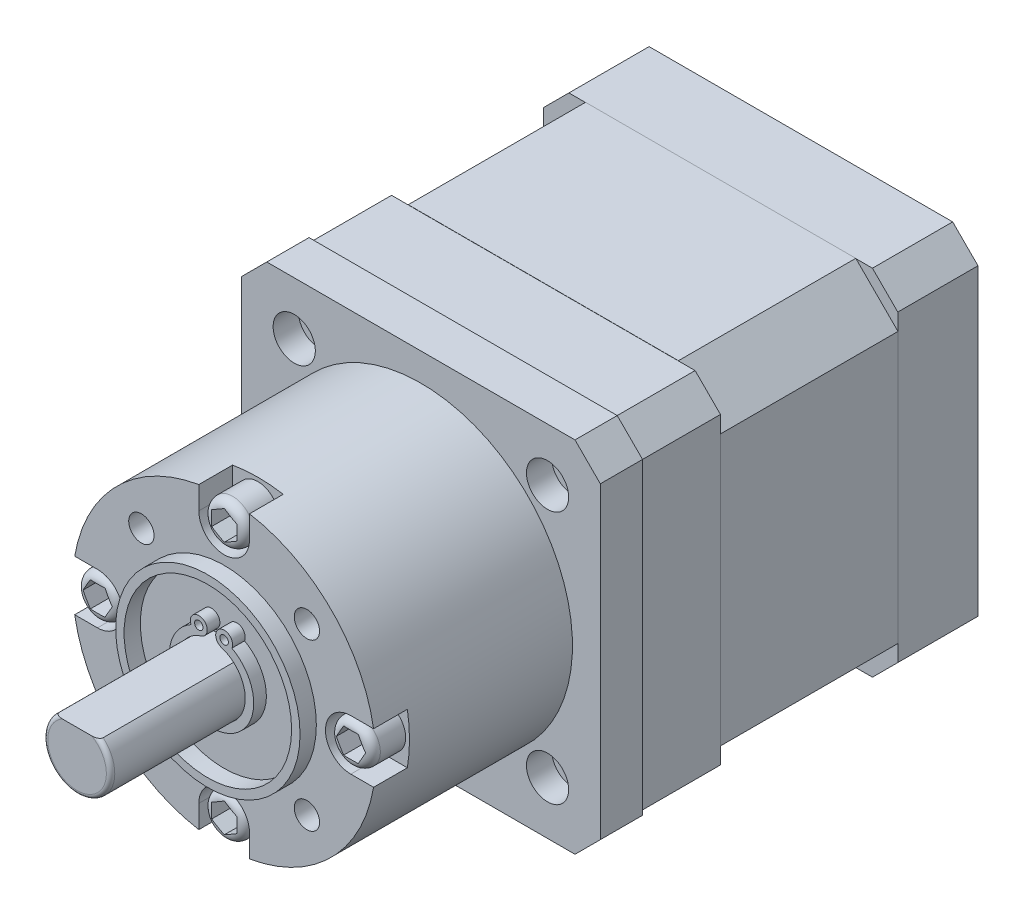
SolidWorks part; units mm, degrees
ref_plane "Front Plane" through (0, 0, 0) normal (0, 0, 1) x (1, 0, 0)
ref_plane "Top Plane" through (0, 0, 0) normal (0, 1, 0) x (1, 0, 0)
ref_plane "Right Plane" through (0, 0, 0) normal (1, 0, 0) x (0, 0, -1)
sketch "Sketch1" plane through (0, 0, 0) normal (0, 0, 1) x (1, 0, 0)
  line L1 (-21, 21) -> (21, 21)
  line L2 (-21, 21) -> (-21, -21)
  line L3 (-21, -21) -> (21, -21)
  line L4 (21, 21) -> (21, -21)
  line L5 (-21, 21) -> (21, -21) construction
  line L6 (-21, -21) -> (21, 21) construction
  point P0 (0, 0)
  dimension "D1" = 42
  dimension "D2" = 42
extrude "Boss-Extrude1" add sketch "Sketch1" along normal blind 21
chamfer "Chamfer1" distance 5 angle 45 4 edges at (-21, -21, 10.5) (-21, 21, 10.5) (21, -21, 10.5) (21, 21, 10.5)
ref_plane "Plane1" through (0, 0, 10.5) normal (0, 0, 1) x (1, 0, 0)
sketch "Sketch2" plane through (0, 0, 21) normal (0, 0, 1) x (1, 0, 0)
  line L1 (-20.975, 20.975) -> (20.975, 20.975)
  line L2 (-20.975, 20.975) -> (-20.975, -20.975)
  line L3 (-20.975, -20.975) -> (20.975, -20.975)
  line L4 (20.975, 20.975) -> (20.975, -20.975)
  line L5 (-20.975, 20.975) -> (20.975, -20.975) construction
  line L6 (-20.975, -20.975) -> (20.975, 20.975) construction
  point P0 (0, 0)
  dimension "D1" = 41.95
extrude "Boss-Extrude2" add sketch "Sketch2" along normal blind 9.5
mirror "Mirror1" about plane through (0, 0, 10.5) normal (0, 0, 1) of "Boss-Extrude2"
sketch "Sketch3" plane through (0, 0, 30.5) normal (0, 0, 1) x (1, 0, 0)
  circle A0 centre (0, 0) radius 17.95
  dimension "D1" = 35.9
extrude "Boss-Extrude3" add sketch "Sketch3" along normal blind 24.3
sketch "Sketch4" plane through (0, 0, -9.5) normal (0, 0, -1) x (-1, 0, 0)
  line L1 (-16, 16) -> (16, 16) construction
  line L2 (-16, 16) -> (-16, -16) construction
  line L3 (-16, -16) -> (16, -16) construction
  line L4 (16, 16) -> (16, -16) construction
  line L5 (-16, 16) -> (16, -16) construction
  line L6 (-16, -16) -> (16, 16) construction
  circle A0 centre (16, 16) radius 2
  circle A1 centre (16, -16) radius 2
  circle A2 centre (-16, -16) radius 2
  circle A3 centre (-16, 16) radius 2
  point P0 (0, 0)
  point P10 (0, 0)
  point P13 (0, 0)
  point P16 (0, 0)
  point P19 (0, 0)
  dimension "D2" = 4
  dimension "D4" = 16
  dimension "D1" = 32
  dimension "D3" = 4
extrude "Cut-Extrude1" cut sketch "Sketch4" against normal blind 1
sketch "Sketch5" plane through (0, 0, -8.5) normal (0, 0, -1) x (-1, 0, 0)
  line L0 (15.75, -14.5) -> (16.25, -14.5)
  line L1 (16.25, 14.5) -> (15.75, 14.5)
  line L2 (16.25, 14.5) -> (16.25, 17.5)
  line L3 (16.25, 17.5) -> (15.75, 17.5)
  line L4 (15.75, 14.5) -> (15.75, 17.5)
  line L5 (16.25, 14.5) -> (15.75, 17.5) construction
  line L6 (16.25, 17.5) -> (15.75, 14.5) construction
  line L7 (14.5, 15.75) -> (17.5, 15.75)
  line L8 (14.5, 15.75) -> (14.5, 16.25)
  line L9 (14.5, 16.25) -> (17.5, 16.25)
  line L10 (17.5, 15.75) -> (17.5, 16.25)
  line L11 (14.5, 15.75) -> (17.5, 16.25) construction
  line L12 (14.5, 16.25) -> (17.5, 15.75) construction
  line L13 (17.5, -16.25) -> (17.5, -15.75)
  line L14 (16.25, -14.5) -> (16.25, -17.5)
  line L15 (14.5, -15.75) -> (17.5, -15.75)
  line L16 (14.5, -16.25) -> (17.5, -16.25)
  line L17 (15.75, -14.5) -> (15.75, -17.5)
  line L18 (14.5, -16.25) -> (14.5, -15.75)
  line L19 (15.75, -17.5) -> (16.25, -17.5)
  line L20 (-14.5, -15.75) -> (-14.5, -16.25)
  line L21 (-16.25, -17.5) -> (-15.75, -17.5)
  line L22 (-14.5, -16.25) -> (-17.5, -16.25)
  line L23 (-15.75, -14.5) -> (-15.75, -17.5)
  line L24 (-16.25, -14.5) -> (-16.25, -17.5)
  line L25 (-14.5, -15.75) -> (-17.5, -15.75)
  line L26 (-16.25, -14.5) -> (-15.75, -14.5)
  line L27 (-17.5, -15.75) -> (-17.5, -16.25)
  line L28 (-15.75, 14.5) -> (-16.25, 14.5)
  line L29 (-17.5, 16.25) -> (-17.5, 15.75)
  line L30 (-16.25, 14.5) -> (-16.25, 17.5)
  line L31 (-14.5, 15.75) -> (-17.5, 15.75)
  line L32 (-14.5, 16.25) -> (-17.5, 16.25)
  line L33 (-15.75, 14.5) -> (-15.75, 17.5)
  line L34 (-14.5, 16.25) -> (-14.5, 15.75)
  line L35 (-15.75, 17.5) -> (-16.25, 17.5)
  point P0 (16, 16)
  point P6 (16, 16)
  point P38 (0, 0)
  dimension "D1" = 3
  dimension "D2" = 0.5
  dimension "D3" = 4
extrude "Cut-Extrude2" cut sketch "Sketch5" against normal blind 2 contours L4 L9 L2 L3 | L9 L8 L7 L4 | L9 L4 L7 L2 | L7 L4 L1 L2 | L7 L10 L9 L2 | L33 L35 L30 L32 | L31 L33 L32 L30 | L30 L32 L29 L31 | L34 L32 L33 L31 | L28 L33 L31 L30 | L26 L24 L25 L23 | L23 L25 L24 L22 | L22 L24 L21 L23 | L25 L27 L22 L24 | L20 L25 L23 L22 | L0 L17 L15 L14 | L15 L17 L16 L14 | L17 L19 L14 L16 | L14 L16 L13 L15 | L18 L16 L17 L15
sketch "Sketch6" plane through (0, 0, 30.5) normal (0, 0, 1) x (1, 0, 0)
  line L1 (-16, -16) -> (16, -16) construction
  line L2 (-16, -16) -> (-16, 16) construction
  line L3 (-16, 16) -> (16, 16) construction
  line L4 (16, -16) -> (16, 16) construction
  line L5 (-16, -16) -> (16, 16) construction
  line L6 (-16, 16) -> (16, -16) construction
  point P0 (0, 0)
  dimension "D1" = 32
sketch "Sketch10" plane through (0, 0, 54.8) normal (0, 0, 1) x (1, 0, 0)
  line L0 (-3, 15) -> (-3, 17.728)
  line L1 (3, 15) -> (3, 17.728)
  line L2 (15, 3) -> (17.728, 3)
  line L3 (15, -3) -> (17.728, -3)
  line L4 (3, -15) -> (3, -17.728)
  line L5 (-3, -15) -> (-3, -17.728)
  line L6 (-15, -3) -> (-17.728, -3)
  line L7 (-15, 3) -> (-17.728, 3)
  line L9 (-8.95, -8.95) -> (8.95, -8.95) construction
  line L10 (-8.95, -8.95) -> (-8.95, 8.95) construction
  line L11 (-8.95, 8.95) -> (8.95, 8.95) construction
  line L12 (8.95, -8.95) -> (8.95, 8.95) construction
  line L13 (-8.95, -8.95) -> (8.95, 8.95) construction
  line L14 (-8.95, 8.95) -> (8.95, -8.95) construction
  circle A0 centre (0, 0) radius 17.98
  circle A1 centre (0, 0) radius 15 construction
  arc A2 (-3, 15) -> (3, 15) centre (0, 15) ccw
  arc A6 (15, 3) -> (15, -3) centre (15, 0) ccw
  arc A7 (3, -15) -> (-3, -15) centre (0, -15) ccw
  arc A8 (-15, -3) -> (-15, 3) centre (-15, 0) ccw
  circle A9 centre (-8.95, 8.95) radius 2 construction
  circle A10 centre (8.95, 8.95) radius 2 construction
  circle A11 centre (8.95, -8.95) radius 2 construction
  circle A12 centre (-8.95, -8.95) radius 2 construction
  point P27 (0, 0)
  point P31 (0, 0)
  dimension "D1" = 35.96
  dimension "D2" = 30
  dimension "D3" = 6
  dimension "D6" = 4
  dimension "D5" = 17.9
  dimension "D4" = 4
extrude "Boss-Extrude4" add sketch "Sketch10" along normal blind 4 contours A8 L6 A0 L5 A7 L4 L3 A6 L2 L1 A2 L0 L7 A12 A11 A10 A9
sketch "Sketch11" plane through (0, 0, 58.8) normal (0, 0, 1) x (1, 0, 0)
  circle A0 centre (0, 0) radius 3.97
  dimension "D1" = 7.94
extrude "Boss-Extrude5" add sketch "Sketch11" along normal blind 17.42
sketch "Sketch12" plane through (0, 0, 76.22) normal (0, 0, 1) x (1, 0, 0)
  line L0 (0, 0) -> (0, 3.97) construction
  line L1 (-2.6002, 3) -> (2.6002, 3)
  circle A0 centre (0, 0) radius 3.97
  circle M2 centre (0, 0) radius 3.97
  dimension "D1" = 7.94
  dimension "D2" = 3
extrude "Cut-Extrude3" cut sketch "Sketch12" against normal blind 18 contours L0 L1 M2 | L1 L0 A0
sketch "Sketch13" plane through (0, 0, 30.5) normal (0, 0, 1) x (1, 0, 0)
  line L1 (-21.25, -21.25) -> (21.25, -21.25)
  line L2 (-21.25, -21.25) -> (-21.25, 21.25)
  line L3 (-21.25, 21.25) -> (21.25, 21.25)
  line L4 (21.25, -21.25) -> (21.25, 21.25)
  line L5 (-21.25, -21.25) -> (21.25, 21.25) construction
  line L6 (-21.25, 21.25) -> (21.25, -21.25) construction
  point P0 (0, 0)
  dimension "D1" = 42.5
extrude "Boss-Extrude6" add sketch "Sketch13" along normal blind 5
sketch "Sketch19" plane through (0, 0, 54.8) normal (0, 0, 1) x (1, 0, 0)
  line L0 (16.7321, 0) -> (15.866, 1.5)
  line L1 (0, 16.7321) -> (-1.5, 15.866)
  line L2 (-1.5, 15.866) -> (-1.5, 14.134)
  line L3 (-1.5, 14.134) -> (0, 13.2679)
  line L4 (0, 13.2679) -> (1.5, 14.134)
  line L5 (1.5, 14.134) -> (1.5, 15.866)
  line L6 (1.5, 15.866) -> (0, 16.7321)
  line L7 (15.866, 1.5) -> (14.134, 1.5)
  line L8 (14.134, 1.5) -> (13.2679, 0)
  line L9 (13.2679, 0) -> (14.134, -1.5)
  line L10 (14.134, -1.5) -> (15.866, -1.5)
  line L11 (15.866, -1.5) -> (16.7321, 0)
  line L12 (0, -16.7321) -> (1.5, -15.866)
  line L13 (1.5, -15.866) -> (1.5, -14.134)
  line L14 (1.5, -14.134) -> (0, -13.2679)
  line L15 (0, -13.2679) -> (-1.5, -14.134)
  line L16 (-1.5, -14.134) -> (-1.5, -15.866)
  line L17 (-1.5, -15.866) -> (0, -16.7321)
  line L18 (-16.7321, 0) -> (-15.866, -1.5)
  line L19 (-15.866, -1.5) -> (-14.134, -1.5)
  line L20 (-14.134, -1.5) -> (-13.2679, 0)
  line L21 (-13.2679, 0) -> (-14.134, 1.5)
  line L22 (-14.134, 1.5) -> (-15.866, 1.5)
  line L23 (-15.866, 1.5) -> (-16.7321, 0)
  circle A0 centre (0, 0) radius 15 construction
  circle A1 centre (0, 15) radius 1.5 construction
  circle A2 centre (0, 15) radius 2.5
  circle A3 centre (15, 0) radius 2.5
  circle A4 centre (0, -15) radius 2.5
  circle A5 centre (-15, 0) radius 2.5
  point P33 (0, 0)
  point P41 (0, 0)
  dimension "D1" = 3
  dimension "D2" = 4
  dimension "D3" = 5
  dimension "D4" = 4
extrude "Boss-Extrude7" add sketch "Sketch19" along normal up to surface (4 mm away) contours A2 | L1 L2 L3 L4 L5 L6 | A3 | L0 L7 L8 L9 L10 L11 | A4 | L12 L13 L14 L15 L16 L17 | A5 | L18 L19 L20 L21 L22 L23 up to face at (0, 0, 58.8)
fillet "Fillet4" radius 1 4 edges at (2.5, -15, 58.8) (-12.5, 0, 58.8) (17.5, 0, 58.8) (2.5, 15, 58.8)
sketch "Sketch20" plane through (0, 0, 58.8) normal (0, 0, 1) x (1, 0, 0)
  line L0 (0, 0) -> (0, 4) construction
  line L1 (-1.5, 4.7697) -> (1.5, 4.7697) construction
  arc A0 (-1.2, 3.8158) -> (1.2, 3.8158) centre (0, 0) ccw
  arc A1 (-2.4192, 4.3758) -> (2.4192, 4.3758) centre (0, 0) ccw
  arc A2 (-1.2, 3.8158) -> (-2.4192, 4.3758) centre (-1.5, 4.7697) ccw
  arc A3 (2.4192, 4.3758) -> (1.2, 3.8158) centre (1.5, 4.7697) ccw
  circle A4 centre (1.5, 4.7697) radius 0.5
  circle A5 centre (-1.5, 4.7697) radius 0.5
  point P8 (0, 4.7697)
  dimension "D2" = 10
  dimension "D3" = 8
  dimension "D4" = 1
  dimension "D1" = 3
extrude "Boss-Extrude8" add sketch "Sketch20" along normal blind 1.5 contours A2 A1 A3 A0 | A4 | A5
sketch "Sketch21" plane through (0, -21, 0) normal (0, -1, 0) x (1, 0, 0)
  line L0 (0, 0) -> (0, -9.5) construction
  line L1 (-4.5, -4) -> (4.5, -4)
  line L2 (-4.5, -4) -> (-4.5, -7)
  line L3 (-4.5, -7) -> (4.5, -7)
  line L4 (4.5, -4) -> (4.5, -7)
  line L5 (-4.5, -4) -> (4.5, -7) construction
  line L6 (-4.5, -7) -> (4.5, -4) construction
  line L7 (-3, -4.5) -> (3, -4.5)
  line L8 (-3, -4.5) -> (-3, -6.5)
  line L9 (-3, -6.5) -> (3, -6.5)
  line L10 (3, -4.5) -> (3, -6.5)
  line L11 (-3, -4.5) -> (3, -6.5) construction
  line L12 (-3, -6.5) -> (3, -4.5) construction
  line L13 (-20.975, -9.5) -> (20.975, -9.5) construction
  point P0 (0, -5.5)
  point P5 (0, -5.5)
  dimension "D1" = 6
  dimension "D2" = 2
  dimension "D3" = 4
  dimension "D4" = 0.5
extrude "Boss-Extrude9" add sketch "Sketch21" along normal blind 1 contours L2 L1 L4 L3 | L8 L7 L10 L9
sketch "Sketch22" plane through (0, -21, 0) normal (0, -1, 0) x (1, 0, 0)
  line L0 (3, -5.5) -> (1.8, -5.5) construction
  line L1 (3, -4.5) -> (3, -6.5) construction
  circle A0 centre (2.3, -5.5) radius 0.5
  dimension "D1" = 1
  dimension "D2" = 0.7
extrude "Boss-Extrude10" add sketch "Sketch22" along normal blind 5
sketch "Sketch23" plane through (0, -21, 0) normal (0, -1, 0) x (1, 0, 0)
  line L0 (3, -5.5) -> (-2.8, -5.5) construction
  line L1 (3, -4.5) -> (3, -6.5) construction
  line L3 (0, -2.983) -> (0, -4.8148) construction
  circle A0 centre (0.7, -5.5) radius 0.5
  circle A1 centre (2.3, -5.5) radius 0.5
  circle A2 centre (-2.3, -5.5) radius 0.5
  circle A3 centre (-0.7, -5.5) radius 0.5
  dimension "D2" = 1
  dimension "D3" = 1
  dimension "D1" = 0.7
extrude "Boss-Extrude11" add sketch "Sketch23" along normal blind 5
chamfer "Chamfer4" distance 3 angle 45 12 edges at (20.975, 20.975, -4.75) (-20.975, 20.975, -4.75) (-20.975, -20.975, -4.75) (20.975, -20.975, -4.75) (20.975, -20.975, 25.75) (21.25, -21.25, 33) (20.975, 20.975, 25.75) (21.25, 21.25, 33) (-21.25, 21.25, 33) (-20.975, 20.975, 25.75) (-20.975, -20.975, 25.75) (-21.25, -21.25, 33)
sketch "Sketch24" plane through (0, 0, 35.5) normal (0, 0, 1) x (1, 0, 0)
  line L1 (-15, -15) -> (15, -15) construction
  line L2 (-15, -15) -> (-15, 15) construction
  line L3 (-15, 15) -> (15, 15) construction
  line L4 (15, -15) -> (15, 15) construction
  line L5 (-15, -15) -> (15, 15) construction
  line L6 (-15, 15) -> (15, -15) construction
  circle A0 centre (-15, 15) radius 2.5
  circle A1 centre (15, 15) radius 2.5
  circle A2 centre (15, -15) radius 2.5
  circle A3 centre (-15, -15) radius 2.5
  point P0 (0, 0)
  dimension "D2" = 5
  dimension "D1" = 30
extrude "Cut-Extrude4" cut sketch "Sketch24" against normal blind 3
sketch "Sketch25" plane through (0, 0, 58.8) normal (0, 0, 1) x (1, 0, 0)
  circle A0 centre (0, 0) radius 10.92
  circle A1 centre (0, 0) radius 9.92
  dimension "D1" = 21.84
  dimension "D2" = 1
extrude "Boss-Extrude12" add sketch "Sketch25" along normal blind 1.93
sketch "Sketch26" plane through (0, 0, 58.8) normal (0, 0, 1) x (1, 0, 0)
  line L1 (9.8, -9.8) -> (-9.8, -9.8) construction
  line L2 (9.8, -9.8) -> (9.8, 9.8) construction
  line L3 (9.8, 9.8) -> (-9.8, 9.8) construction
  line L4 (-9.8, -9.8) -> (-9.8, 9.8) construction
  line L5 (9.8, -9.8) -> (-9.8, 9.8) construction
  line L6 (9.8, 9.8) -> (-9.8, -9.8) construction
  circle A0 centre (-9.8, 9.8) radius 1.5
  circle A1 centre (9.8, 9.8) radius 1.5
  circle A2 centre (9.8, -9.8) radius 1.5
  circle A3 centre (-9.8, -9.8) radius 1.5
  point P0 (0, 0)
  point P16 (0, 0)
  dimension "D3" = 3
  dimension "D1" = 19.6
  dimension "D2" = 19.6
  dimension "D4" = 4
extrude "Cut-Extrude5" cut sketch "Sketch26" against normal blind 7.3
fillet "Fillet5" radius 0.5 1 edges at (0, -3.97, 76.22)
